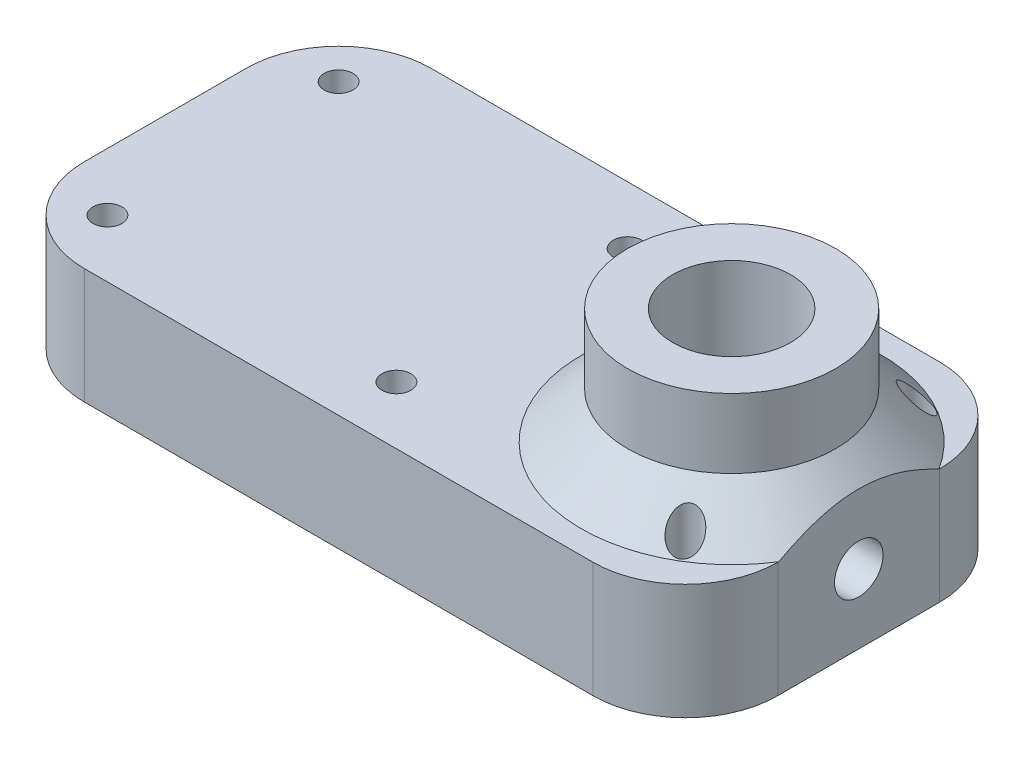
SolidWorks part; units mm, degrees
material "Aluminum 101"
ref_plane "Front Plane" through (0, 0, 0) normal (0, 0, 1) x (1, 0, 0)
ref_plane "Top Plane" through (0, 0, 0) normal (0, 1, 0) x (1, 0, 0)
ref_plane "Right Plane" through (0, 0, 0) normal (1, 0, 0) x (0, 0, -1)
sketch "Sketch1" plane through (0, 0, 0) normal (0, 1, 0) x (1, 0, 0)
  line L1 (-49, 15) -> (11, 15)
  line L2 (-49, 15) -> (-49, -15)
  line L3 (-49, -15) -> (11, -15)
  line L4 (11, 15) -> (11, -15)
  circle A1 centre (0, 0) radius 9
  point P8 (11, 0)
  dimension "D2" = 18
  dimension "D3" = 30
  dimension "D4" = 60
  dimension "D1" = 11
extrude "Base" add sketch "Sketch1" along normal blind 10 contours L4 A1 L1 L2 L3 | A1 region at (-22.1283, 0, 0) region at (0, 0, 0)
fillet "AddALittleBeauty" radius 8 4 edges at (-49, 5, 15) (-49, 5, -15) (11, 5, -15) (11, 5, 15)
extrude "RodHolder" add sketch "Sketch1<3>" along normal blind 20 contours A1 region at (0, 0, 0)
sketch "Sketch1<3>" plane through (0, 0, 0) normal (0, 1, 0) x (1, 0, 0) same geometry as "Sketch1"
hole_wizard "M5x0.8 Tapped Hole for fixing rod" positions "Sketch3" profile "Sketch4" tap size "M5x0.8" standard "ANSI Metric"
sketch "Sketch3" plane through (11, 0, 0) normal (1, 0, 0) x (0, 0, -1)
  line L0 (7, 0) -> (-7, 0) construction
  point P0 (0, 6)
  dimension "D1" = 6
cosmetic thread "Hole Thread1" parameters "D1"=6.3524, "D2"=5
sketch "Sketch4" plane through (11, 6, 0) normal (0, 1, 0) x (0, 0, -1)
  line L0 (0, 0) -> (0, 11.6618)
  line L1 (0, 11.6618) -> (2.1, 10.4)
  line L2 (2.1, 10.4) -> (2.1, 0)
  line L5 (2.1, 0) -> (0, 0)
  line L10 (0, 11.6618) -> (-2.1, 10.4) construction
  line L11 (0, -6.35) -> (0, 107.95) construction
  dimension "Tap Drill Dia." = 4.2
  dimension "Tap Drill Depth" = 10.4
  dimension "Drill Angle" = 118
chamfer "Chamfer1" distance 4 angle 45 1 edges at (0, 10, 9)
hole_wizard "Ø10.2 (10.2) Rod Hole" positions "Sketch5" profile "Sketch6" hole size "Ø10.2" standard "ANSI Metric" end condition through all
sketch "Sketch5" plane through (0, 20, 0) normal (0, 1, 0) x (1, 0, 0)
  point P0 (0, 0)
sketch "Sketch6" plane through (0, 20, 0) normal (1, 0, 0) x (0, 0, 1)
  line L0 (0, 0) -> (0, 20)
  line L1 (0, 20) -> (5.1, 20)
  line L2 (5.1, 20) -> (5.1, 0)
  line L5 (5.1, 0) -> (0, 0)
  line L11 (0, -6.35) -> (0, 107.95) construction
  dimension "Thru Hole Dia." = 10.2
  dimension "Thru Hole Depth" = 20
hole_wizard "M3x0.5 Tapped Hole1" positions "Sketch7" profile "Sketch8" tap size "M3x0.5" standard "ANSI Metric" end condition through all
sketch "Sketch7" plane through (0, 0, 0) normal (0, -1, 0) x (-1, 0, 0)
  line L0 (41, 15) -> (-3, 15) construction
  line L2 (49, 7) -> (49, -7) construction
  line L4 (19, 18.3865) -> (19, -17.1189) construction
  line L5 (49, 0) -> (41.0253, 0) construction
  point P0 (-6, 10)
  point P3 (-6, -10)
  point P6 (44, -10)
  point P9 (44, 10)
  point P27 (19, 10)
  point P29 (19, -10)
  point P39 (19, 15)
  dimension "D1" = 20
  dimension "D2" = 25
  dimension "D3" = 25
sketch "Sketch8" plane through (6, 0, -10) normal (1, 0, 0) x (0, 0, -1)
  line L0 (0, 0) -> (0, 20)
  line L1 (0, 20) -> (1.25, 20)
  line L2 (1.25, 20) -> (1.25, 0.275)
  line L3 (1.25, 0.275) -> (1.525, 0)
  line L5 (1.525, 0) -> (0, 0)
  line L6 (-1.25, 0.275) -> (-1.525, 0) construction
  line L11 (0, -6.35) -> (0, 107.95) construction
  dimension "Thru Tap Drill Dia." = 2.5
  dimension "Thru Tap Drill Depth" = 20
  dimension "Near C'Sink Dia." = 3.05
  dimension "Near C'Sink Angle" = 90
cosmetic thread "Hole Thread2" parameters "D2"=3
cosmetic thread "Hole Thread3" parameters "D2"=3
cosmetic thread "Hole Thread4" parameters "D2"=3
cosmetic thread "Hole Thread5" parameters "D2"=3
cosmetic thread "Hole Thread6" parameters "D2"=3
cosmetic thread "Hole Thread7" parameters "D2"=3
sketch "Sketch9" plane through (0, 0, 0) normal (0, -1, 0) x (1, 0, 0)
  line L0 (-49, -7) -> (-49, 7) construction
  circle A0 centre (-31, 0) radius 10
  point P4 (0, 0)
  dimension "D1" = 20
  dimension "D2" = 18
extrude "Cut-Extrude1" cut sketch "Sketch9" against normal blind 4
equation "\"D2@Sketch1\"=10.00mm+8"
